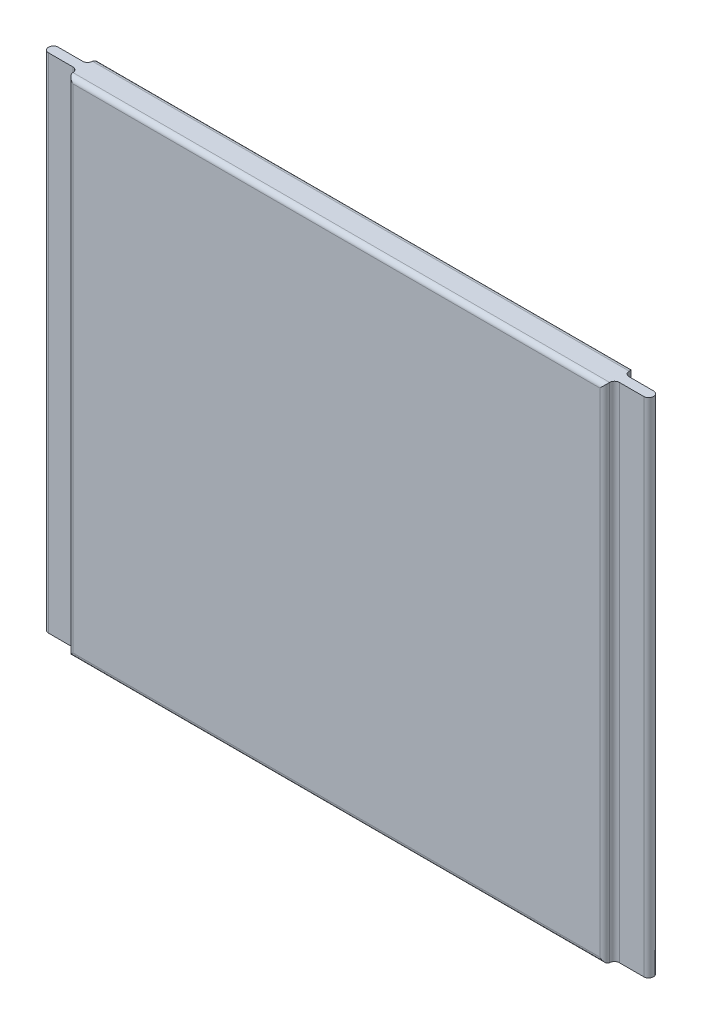
SolidWorks part; units mm, degrees
ref_plane "Front Plane" through (0, 0, 0) normal (0, 0, 1) x (1, 0, 0)
ref_plane "Top Plane" through (0, 0, 0) normal (0, 1, 0) x (1, 0, 0)
ref_plane "Right Plane" through (0, 0, 0) normal (1, 0, 0) x (0, 0, -1)
sketch "Sketch2" plane through (0, 0, 0) normal (0, 1, 0) x (1, 0, 0)
  line L0 (0, 3) -> (0, -3) construction
  line L1 (-55, 3) -> (55, 3)
  line L2 (-55, 3) -> (-55, 2)
  line L3 (-55, -3) -> (55, -3)
  line L4 (55, 3) -> (55, 2)
  line L5 (-55, 3) -> (55, -3) construction
  line L6 (-55, -3) -> (55, 3) construction
  line L7 (-56, 1) -> (-61, 1)
  line L9 (-56, -1) -> (-61, -1)
  line L11 (-55, -2) -> (-55, -3)
  line L12 (56, -1) -> (61, -1)
  line L14 (56, 1) -> (61, 1)
  line L15 (55, -2) -> (55, -3)
  arc A2 (-55, -2) -> (-56, -1) centre (-56, -2) ccw
  arc A3 (-55, 2) -> (-56, 1) centre (-56, 2) cw
  arc A4 (55, -2) -> (56, -1) centre (56, -2) cw
  arc A7 (55, 2) -> (56, 1) centre (56, 2) ccw
  arc A8 (-61, 1) -> (-61, -1) centre (-61, 0) ccw
  arc A9 (61, 1) -> (61, -1) centre (61, 0) cw
  point P0 (0, 0)
  point P9 (-62, 0)
  point P20 (-55, -1)
  dimension "D6" = 2
  dimension "D7" = 62
  dimension "D8" = 1
  dimension "D9" = 1
  dimension "D3" = 0
  dimension "D4" = 0
  dimension "D1" = 110
  dimension "D2" = 2
  dimension "D5" = 2
extrude "Boss-Extrude1" add sketch "Sketch2" along normal blind 103
fillet "Fillet1" radius 1 8 edges at (55, 51.5, -3) (0, 103, -3) (-55, 51.5, -3) (0, 0, -3) (-55, 51.5, 3) (0, 103, 3) (55, 51.5, 3) (0, 0, 3)
